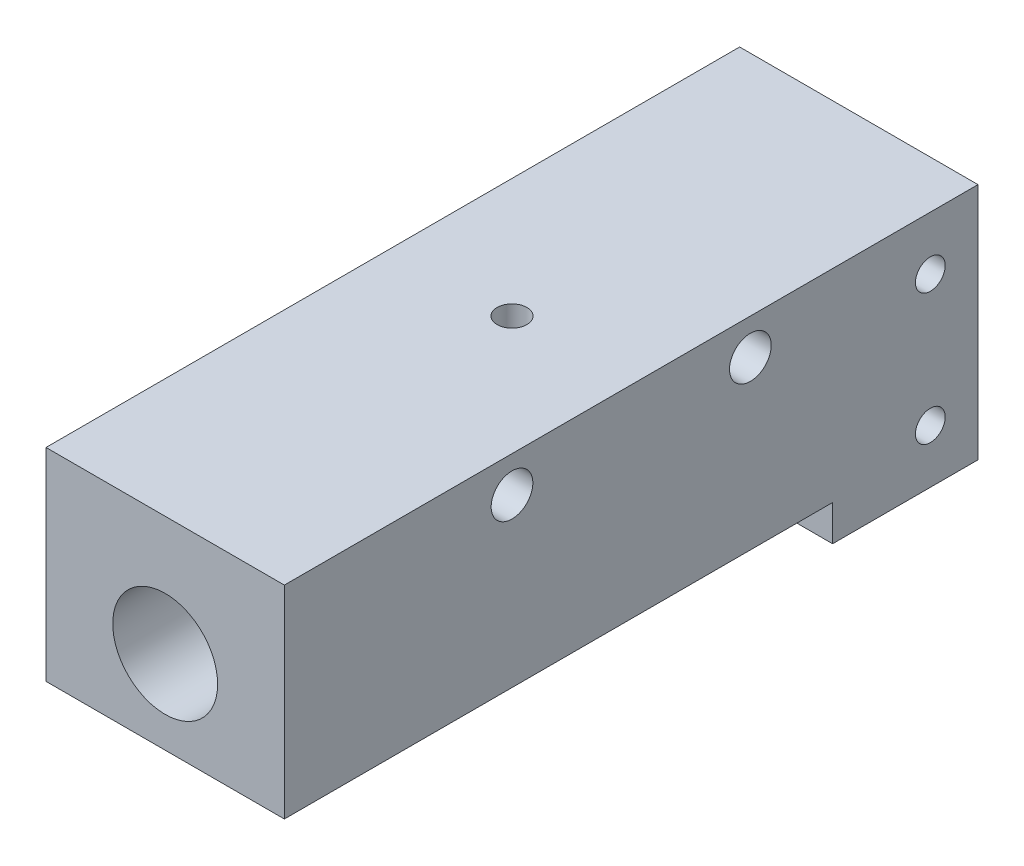
SolidWorks part; units mm, degrees
material "6063-T5"
ref_plane "Piano frontale" through (0, 0, 0) normal (0, 0, 1) x (1, 0, 0)
ref_plane "Piano superiore" through (0, 0, 0) normal (0, 1, 0) x (1, 0, 0)
ref_plane "Piano destro" through (0, 0, 0) normal (1, 0, 0) x (0, 0, -1)
sketch "Schizzo1" plane through (0, 0, 0) normal (0, 0, 1) x (1, 0, 0)
  line L1 (10, -10) -> (-10, -10)
  line L2 (10, -10) -> (10, 10)
  line L3 (10, 10) -> (-10, 10)
  line L4 (-10, -10) -> (-10, 10)
  line L5 (10, -10) -> (-10, 10) construction
  line L6 (10, 10) -> (-10, -10) construction
  point P0 (0, 0)
  dimension "D1" = 20
  dimension "D2" = 20
extrude "Estrusione-Estrusione1" add sketch "Schizzo1" against normal blind 58.2
sketch "Schizzo2" plane through (0, 0, -58.2) normal (0, 0, -1) x (-1, 0, 0)
  circle A0 centre (0, 0) radius 3
  dimension "D1" = 6
extrude "Taglio-Estrusione1" cut sketch "Schizzo2" against normal through all
sketch "Schizzo3" plane through (0, 0, -58.2) normal (0, 0, -1) x (-1, 0, 0)
  point P0 (0, 0)
sketch "Schizzo4" plane through (10, 0, 0) normal (1, 0, 0) x (0, 0, -1)
  line L0 (0, 7) -> (58.2, 7) construction
  line L1 (0, -10) -> (0, 10) construction
  line L2 (58.2, -10) -> (58.2, 10) construction
  line L3 (58.2, 10) -> (0, 10) construction
  line L4 (29.1, 10) -> (29.1, -10) construction
  line L5 (58.2, -10) -> (0, -10) construction
  circle A0 centre (19.1, 7) radius 1.75
  circle A1 centre (39.1, 7) radius 1.75
  dimension "D2" = 3.5
  dimension "D1" = 3
  dimension "D3" = 10
extrude "Taglio-Estrusione3" cut sketch "Schizzo4" against normal through all
hole_wizard "Foro filettato G1/8-1" positions "Schizzo8" profile "Schizzo7" tap size "G1/8" standard "BSI"
sketch "Schizzo8" plane through (0, 0, 0) normal (0, 0, 1) x (1, 0, 0)
  point P0 (0, 0)
sketch "Schizzo7" plane through (0, 0, 0) normal (1, 0, 0) x (0, -1, 0)
  line L0 (0, 0) -> (0, 12.6438)
  line L1 (0, 12.6438) -> (4.4, 10)
  line L2 (4.4, 10) -> (4.4, 0)
  line L5 (4.4, 0) -> (0, 0)
  line L10 (0, 12.6438) -> (-4.4, 10) construction
  line L11 (0, -6.35) -> (0, 107.95) construction
  dimension "Tap Drill Dia." = 8.8
  dimension "Tap Drill Depth" = 10
  dimension "Drill Angle" = 118
sketch "Schizzo10" plane through (10, 0, 0) normal (1, 0, 0) x (0, 0, -1)
  line L0 (0, -7) -> (46, -7)
  line L1 (0, -10) -> (0, 10) construction
  line L2 (46, -7) -> (46, -10)
  line L3 (58.2, -10) -> (0, -10) construction
  dimension "D1" = 46
  dimension "D2" = 3
extrude "Taglio-Estrusione5" cut sketch "Schizzo10" against normal through all and the other way through all flip side to cut
sketch "Schizzo11" plane through (0, 10, 0) normal (0, 1, 0) x (1, 0, 0)
  line L0 (0, 58.2) -> (0, 0) construction
  line L1 (10, 58.2) -> (-10, 58.2) construction
  line L2 (10, 29.1) -> (-10, 29.1) construction
  line L3 (10, 58.2) -> (10, 0) construction
  point P10 (0, 29.1)
  point P11 (0, 29.1)
  point P12 (0, 29.1)
hole_wizard "Foro filettato M3-1" positions "Schizzo3D1" profile "Schizzo12" tap size "M3" standard "DIN"
sketch3d "Schizzo3D1"
  point P0 (0, 10, -29.1)
sketch "Schizzo12" plane through (0, 10, -29.1) normal (1, 0, 0) x (0, 0, 1)
  line L0 (0, 0) -> (0, 5.7511)
  line L1 (0, 5.7511) -> (1.25, 5)
  line L2 (1.25, 5) -> (1.25, 0)
  line L5 (1.25, 0) -> (0, 0)
  line L10 (0, 5.7511) -> (-1.25, 5) construction
  line L11 (0, -6.35) -> (0, 107.95) construction
  dimension "Tap Drill Dia." = 2.5
  dimension "Tap Drill Depth" = 5
  dimension "Drill Angle" = 118
hole_wizard "Foro Ø16.0 (16)-1" positions "Schizzo3D3" profile "Schizzo14" hole size "Ø16.0" standard "ISO"
sketch3d "Schizzo3D3"
  point P0 (0, 0, 0)
  point P3 (0, 0, -58.2)
sketch "Schizzo14" plane through (0, 0, -58.2) normal (1, 0, 0) x (0, 1, 0)
  line L0 (0, 0) -> (0, 15.8069)
  line L1 (0, 15.8069) -> (8, 11)
  line L2 (8, 11) -> (8, 0)
  line L5 (8, 0) -> (0, 0)
  line L10 (0, 15.8069) -> (-8, 11) construction
  line L11 (0, -6.35) -> (0, 107.95) construction
  dimension "Hole Dia." = 16
  dimension "Hole Depth" = 11
  dimension "Drill Angle" = 118
sketch "Schizzo15" plane through (10, 0, 0) normal (1, 0, 0) x (0, 0, -1)
  line L0 (47.2, 0) -> (58.2, 0) construction
  line L1 (47.2, 8) -> (47.2, -8) construction
  line L4 (58.2, -10) -> (58.2, 10) construction
  line L6 (58.2, -10) -> (46, -10) construction
  point P5 (54.2, -5.5)
  point P8 (54.2, 5.5)
  point P11 (56.209, -10)
  dimension "D1" = 5.5
  dimension "D2" = 7
  dimension "D3" = 4
  dimension "D4" = 4.5
hole_wizard "Foro filettato M3-2" positions "Schizzo3D4" profile "Schizzo16" tap size "M3" standard "ISO" end condition through all
sketch3d "Schizzo3D4"
  point P0 (10, 5.5, -54.2)
  point P3 (10, -5.5, -54.2)
sketch "Schizzo16" plane through (10, 5.5, -54.2) normal (0, 1, 0) x (0, 0, -1)
  line L0 (0, 0) -> (0, 20)
  line L1 (0, 20) -> (1.25, 20)
  line L2 (1.25, 20) -> (1.25, 0)
  line L5 (1.25, 0) -> (0, 0)
  line L11 (0, -6.35) -> (0, 107.95) construction
  dimension "Thread Major Dia." = 2.5
  dimension "Thru Tap Drill Depth" = 20
